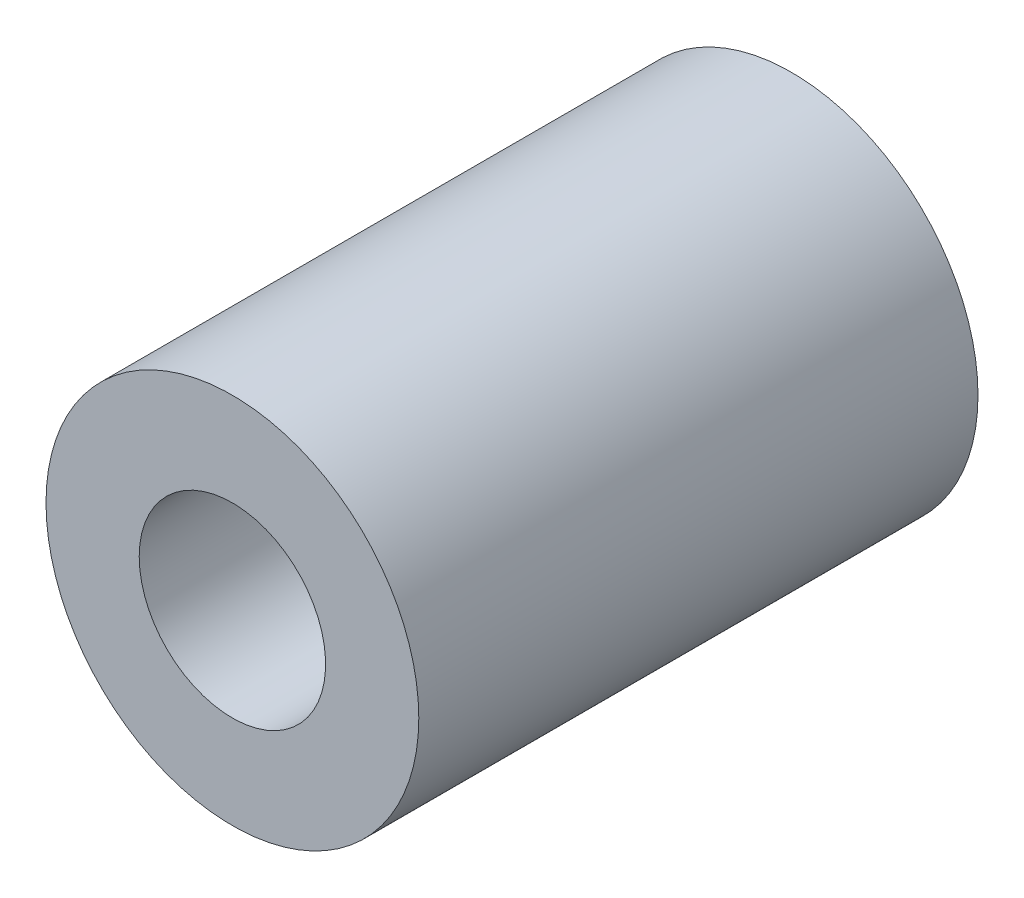
SolidWorks part; units mm, degrees
ref_plane "Front Plane" through (0, 0, 0) normal (0, 0, 1) x (1, 0, 0)
ref_plane "Top Plane" through (0, 0, 0) normal (0, 1, 0) x (1, 0, 0)
ref_plane "Right Plane" through (0, 0, 0) normal (1, 0, 0) x (0, 0, -1)
sketch "Sketch1" plane through (0, 0, 0) normal (0, 0, 1) x (1, 0, 0)
  circle A0 centre (0, 0) radius 1.5875
  circle A1 centre (0, 0) radius 3.175
  dimension "D1" = 6.35
  dimension "D2" = 3.175
extrude "Boss-Extrude1" add sketch "Sketch1" along normal blind 9.525
scale "Scale1" scale about centroid uniform scaling yes scale factor 0.75
equation "\"large_diameter\" = 1/4in"
equation "\"small_diameter\" = 1/8in"
equation "\"arc_height\" = 1/32in"
equation "\"chain_space\" = 1/2in"
equation "\"chain_thickness\" = 1/16in"
equation "\"outer_height\" = 3/16in"
equation "\"inner_height\" = 2/16in"
equation "\"give\" = 1/16in"
equation "\"board_base\" = 10"
equation "\"board_rows\" = 3"
equation "\"num_links\"=1"
equation "\"D1@Sketch1\"=\"large_diameter\""
equation "\"D2@Sketch1\"=\"small_diameter\""
equation "\"D1@Boss-Extrude1\"=\"outer_height\"+\"chain_thickness\"*2+\"give\""
